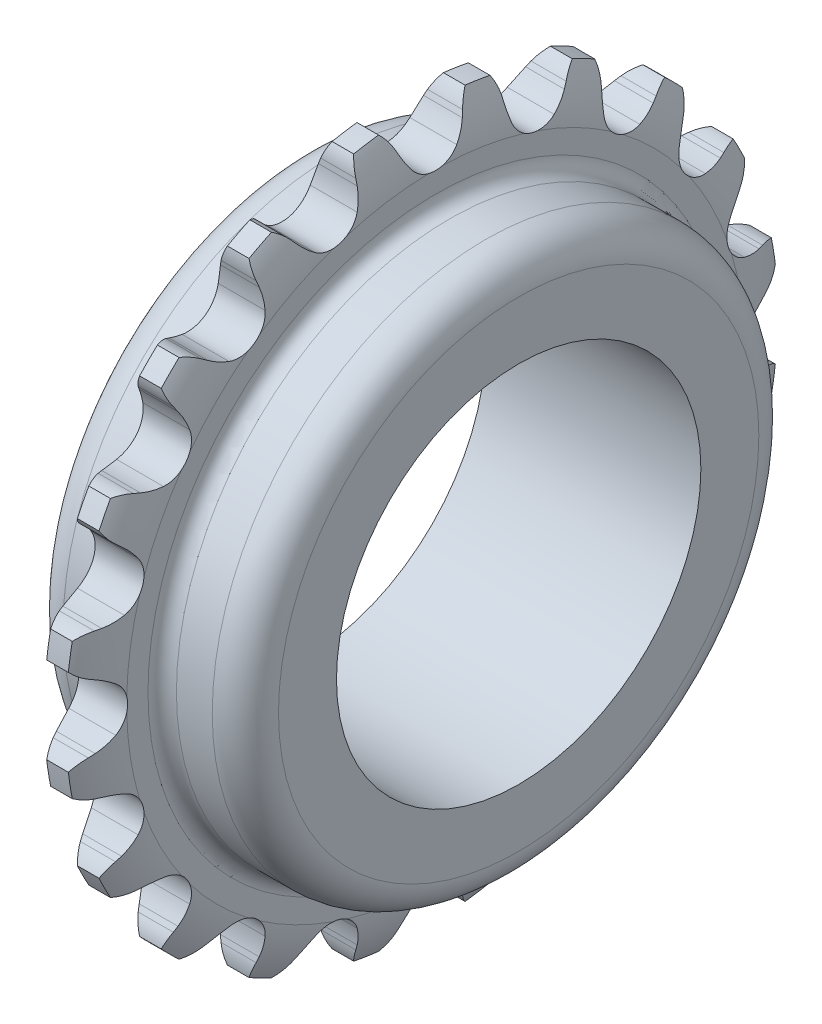
SolidWorks part; units mm, degrees
material "AISI 1020"
ref_plane "Front" through (0, 0, 0) normal (0, 0, 1) x (1, 0, 0)
ref_plane "Top" through (0, 0, 0) normal (0, 1, 0) x (1, 0, 0)
ref_plane "Right" through (0, 0, 0) normal (1, 0, 0) x (0, 0, -1)
sketch "Sketch1" plane through (0, 0, 0) normal (0, 0, 1) x (1, 0, 0)
  line L0 (-4, 0) -> (4, 0) construction
  line L1 (-2.5517, 0) -> (-2.5517, 16.5)
  line L2 (-2.5517, 16.5) -> (-2.3371, 16.5)
  line L3 (-1.4787, 17.3584) -> (-1.4787, 18.646)
  line L4 (-0.6532, 21.5) -> (0.6532, 21.5)
  line L5 (1.4787, 18.646) -> (1.4787, 17.3584)
  line L6 (2.3371, 16.5) -> (2.5517, 16.5)
  line L7 (2.5517, 16.5) -> (2.5517, 0)
  line L8 (2.5517, 0) -> (-2.5517, 0)
  line L9 (0, 0) -> (0, 21.5) construction
  line L10 (-1.1821, 20.296) -> (1.1821, 20.296) construction
  line L11 (-1.1821, -20.296) -> (1.1821, -20.296) construction
  line L13 (-1.4787, 18.646) -> (3.7984, 18.646) construction
  line L14 (-1.4787, -18.646) -> (3.7984, -18.646) construction
  arc A0 (-0.6532, 21.5) -> (-1.4787, 18.646) centre (4.8647, 18.3576) ccw
  arc A1 (0.6532, 21.5) -> (1.4787, 18.646) centre (-4.8647, 18.3576) cw
  arc A2 (1.4787, 17.3584) -> (2.3371, 16.5) centre (2.3371, 17.3584) ccw
  arc A3 (-2.3371, 16.5) -> (-1.4787, 17.3584) centre (-2.3371, 17.3584) ccw
  point P30 (1.4787, 16.5)
  point P33 (-1.4787, 16.5)
  point P34 (24, 26.331)
  point P36 (27.3, 26.331)
  point P37 (24, 21.8279)
  point P38 (30, 21.8279)
  point P39 (24, 17.1531)
  point P40 (27.18, 17.1531)
  point P41 (24, 13.3224)
  point P42 (30.4, 13.3224)
  point P43 (24, 30.8002)
  point P44 (44, 30.8002)
  point P45 (24, 35.1098)
  point P46 (30.35, 35.1098)
  dimension "D1" = 2.146
  dimension "rx" = 6.35
  dimension "D3" = 0.8584
  dimension "d" = 40.5921
  dimension "p" = 6.35
  dimension "z" = 20
  dimension "da" = 43
  dimension "df" = 37.2921
  dimension "dr" = 3.3
  dimension "dg" = 33
  dimension "h" = 6
  dimension "bf1" = 2.9574
  dimension "b1" = 3.18
  dimension "ba" = 0.8255
  dimension "D2" = 1.073
  dimension "pt" = 6.4
revolve "Revolve" add sketch "Sketch1" angle 360 about L0
ref_axis "Axis1" through (-8.5448, 0, 0) along (1, 0, 0)
sketch "Sketch2" plane through (0, 0, 0) normal (1, 0, 0) x (0, 0, -1)
  line L0 (0, 0) -> (0, 21.5) construction
  line L1 (0, 0) -> (-3.3633, 21.2353) construction
  line L2 (0, 0) -> (-6.6439, 20.4477) construction
  line L3 (1.3461, 19.2443) -> (-5.6977, 24.7476) construction
  line L4 (1.9281, 20.2364) -> (-2.0803, 21.9214) construction
  line L5 (0, 0) -> (3.3633, 21.2353) construction
  line L6 (1.9281, 20.2364) -> (2.0565, 20.5416)
  line L7 (-1.9281, 20.2364) -> (-2.0565, 20.5416)
  circle A0 centre (0, 0) radius 21.5 construction
  arc A1 (1.3461, 19.2443) -> (-1.3461, 19.2443) centre (0, 20.296) cw
  arc A2 (1.3461, 19.2443) -> (1.9281, 20.2364) centre (-2.0803, 21.9214) ccw
  arc A3 (2.6091, 21.3411) -> (2.0565, 20.5416) centre (4.2372, 19.6249) ccw
  arc A4 (-1.3461, 19.2443) -> (-1.9281, 20.2364) centre (2.0803, 21.9214) cw
  arc A5 (-2.6091, 21.3411) -> (-2.0565, 20.5416) centre (-4.2372, 19.6249) cw
  arc A7 (2.6091, 21.3411) -> (-2.6091, 21.3411) centre (0, 0) ccw
  dimension "r1" = 1.7083
  dimension "r3" = 2.3656
  dimension "D1" = 18
  dimension "D2" = 9
  dimension "av2" = 52
  dimension "M" = 2.0803
  dimension "T" = 1.6253
  dimension "beta" = 15.2
  dimension "yv2" = 13.8
  dimension "bc" = 0.3311
extrude "ExtrudeCutOne" cut sketch "Sketch2" against normal mid plane 5.1034
pattern_circular "PatternOne" count 20 over 360 about axis through (-4, 0, 0) along (1, 0, 0) of "ExtrudeCutOne"
sketch "SketchHole" plane through (0, 0, 0) normal (1, 0, 0) x (0, 0, -1)
  circle A0 centre (0, 0) radius 5
extrude "Cut-ExtrudeA" cut sketch "SketchHole" against normal through all and the other way through all
sketch "SketchKey" plane through (0, 0, 0) normal (1, 0, 0) x (0, 0, -1)
  line L1 (-1.5, 2.5) -> (1.5, 2.5)
  line L2 (-1.5, 2.5) -> (-1.5, 6.4)
  line L3 (-1.5, 6.4) -> (1.5, 6.4)
  line L4 (1.5, 2.5) -> (1.5, 6.4)
extrude "Cut-ExtrudeB" cut sketch "SketchKey" against normal through all and the other way through all
sketch "草图1" plane through (2.5517, 0, 0) normal (1, 0, 0) x (0, 0, -1)
  circle A0 centre (0, 0) radius 6.5734
extrude "凸台-拉伸1" add sketch "草图1" against normal up to surface (5.1034 mm away) up to face at (-2.5517, 3.1424, 0)
sketch "草图3" plane through (0, 0, 0) normal (1, 0, 0) x (0, 0, -1)
  circle A0 centre (0, 0) radius 16.5
  dimension "D1" = 33
extrude "凸台-拉伸2" add sketch "草图3" along normal mid plane 13
sketch "草图4" plane through (6.5, 0, 0) normal (1, 0, 0) x (0, 0, -1)
  circle A0 centre (0, 0) radius 11
  dimension "D1" = 22
extrude "切除-拉伸1" cut sketch "草图4" against normal mid plane 85
fillet "圆角1" radius 2 2 edges at (-6.5, 0, -16.5) (6.5, 0, -16.5)
sketch "草图5" plane through (0, 0, 0) normal (1, 0, 0) x (0, 0, -1)
  circle A0 centre (0, 0) radius 24.5537
  dimension "D1" = 49.1073
extrude "切除-拉伸2" [suppressed] cut sketch "草图5" against normal blind 85 from offset 1.5 offset against normal yes
mirror "镜向1" [suppressed] about plane through (0, 0, 0) normal (1, 0, 0)
sketch "草图6" [suppressed] plane through (1.5, 0, 0) normal (1, 0, 0) x (0, 0, -1)
  circle A0 centre (0, 0) radius 6.5734
extrude "凸台-拉伸3" [suppressed] add sketch "草图6" against normal up to surface (3 mm away)
sketch "草图7" [suppressed] plane through (1.5, 0, 0) normal (1, 0, 0) x (0, 0, -1)
  circle A0 centre (0, 0) radius 15
  dimension "D1" = 30
extrude "凸台-拉伸4" [suppressed] add sketch "草图7" along normal blind 12
sketch "草图8" [suppressed] plane through (13.5, 0, 0) normal (1, 0, 0) x (0, 0, -1)
  circle A0 centre (0, 0) radius 5
  dimension "D1" = 10
extrude "切除-拉伸3" [suppressed] cut sketch "草图8" against normal blind 31
fillet "圆角2" [suppressed] radius 2
